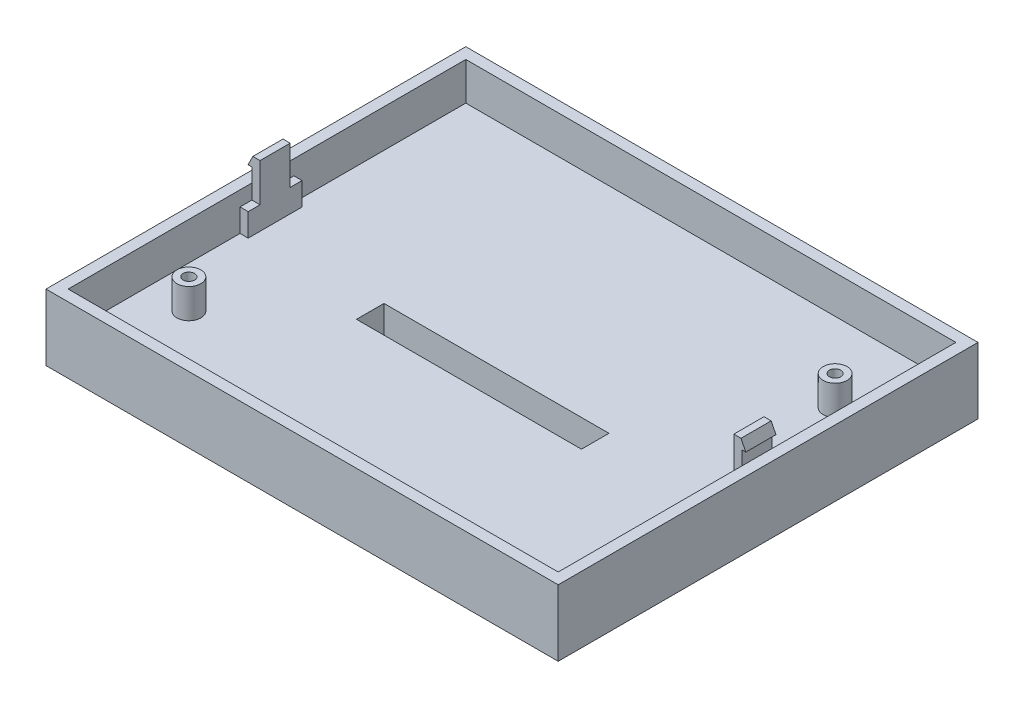
SolidWorks part; units mm, degrees
ref_plane "Alzado" through (0, 0, 0) normal (0, 0, 1) x (1, 0, 0)
ref_plane "Planta" through (0, 0, 0) normal (0, 1, 0) x (1, 0, 0)
ref_plane "Vista lateral" through (0, 0, 0) normal (1, 0, 0) x (0, 0, -1)
sketch "Sketch1" plane through (0, 0, 0) normal (0, 1, 0) x (1, 0, 0)
  line L1 (-53.5, -43.85) -> (53.5, -43.85)
  line L2 (-53.5, -43.85) -> (-53.5, 43.85)
  line L3 (-53.5, 43.85) -> (53.5, 43.85)
  line L4 (53.5, -43.85) -> (53.5, 43.85)
  line L5 (-53.5, -43.85) -> (53.5, 43.85) construction
  line L6 (-53.5, 43.85) -> (53.5, -43.85) construction
  point P0 (0, 0)
  dimension "D1" = 107
  dimension "D2" = 87.7
extrude "Boss-Extrude1" add sketch "Sketch1" along normal blind 13.85
sketch "Sketch2" plane through (0, 13.85, 0) normal (0, 1, 0) x (1, 0, 0)
  line L8 (51.19, -41.54) -> (51.19, 41.54)
  line L9 (51.19, 41.54) -> (-51.19, 41.54)
  line L10 (-51.19, 41.54) -> (-51.19, -41.54)
  line L11 (-51.19, -41.54) -> (51.19, -41.54)
  line L12 (51.19, -41.54) -> (51.19, 41.54)
  line L13 (51.19, 41.54) -> (-51.19, 41.54)
  line L14 (-51.19, 41.54) -> (-51.19, -41.54)
  line L15 (-51.19, -41.54) -> (51.19, -41.54)
  dimension "D1" = 2.31
extrude "Cut-Extrude1" cut sketch "Sketch2" against normal blind 7.9
sketch "Sketch3" plane through (0, 0, 0) normal (0, -1, 0) x (1, 0, 0)
  line L1 (-23.5, 14.74) -> (23.5, 14.74)
  line L7 (-23.5, 14.74) -> (-23.5, 3.2453)
  line L12 (53.5, 43.85) -> (53.5, -43.85) construction
  line L13 (53.5, -20.56) -> (53.5, 17.44)
  line L14 (0, 0) -> (0, 18.4212) construction
  line L23 (-6.19, -43.85) -> (6.19, -43.85)
  line L26 (53.5, -43.85) -> (-53.5, -43.85) construction
  line L27 (-23.5, 3.2453) -> (23.5, 3.2453)
  line L45 (23.5, 3.2453) -> (23.5, 14.74)
sketch "Sketch4" plane through (0, 5.95, 0) normal (0, 1, 0) x (1, 0, 0)
  circle A0 centre (42.5, 25) radius 1.2
  circle A1 centre (-42.5, -25) radius 1.2
  circle A2 centre (-42.5, -25) radius 2.5
  circle A3 centre (42.5, 25) radius 2.5
  dimension "D1" = 2.4
  dimension "D6" = 5
  dimension "D2" = 25
  dimension "D3" = 25
  dimension "D4" = 42.5
  dimension "D5" = 42.5
extrude "Boss-Extrude2" add sketch "Sketch4" along normal blind 6.2
sketch "Sketch7" plane through (-51.19, 0, 0) normal (1, 0, 0) x (0, 0, -1)
  line L0 (41.54, 5.95) -> (-41.54, 5.95) construction
  line L1 (-5.625, 5.95) -> (5.625, 5.95)
  line L2 (-5.625, 5.95) -> (-5.625, 10.75)
  line L3 (-5.625, 10.75) -> (5.625, 10.75)
  line L4 (5.625, 5.95) -> (5.625, 10.75)
  point P6 (0, 5.95)
  dimension "D1" = 11.25
  dimension "D2" = 4.8
extrude "Boss-Extrude3" add sketch "Sketch7" along normal blind 1.7
sketch "Sketch8" plane through (0, 0, 0) normal (0, 0, 1) x (1, 0, 0)
  line L0 (-49.49, 10.75) -> (-49.49, 18.75)
  line L1 (-49.49, 18.75) -> (-50.99, 18.75)
  line L2 (-50.99, 18.75) -> (-51.99, 16.75)
  line L3 (-51.99, 16.75) -> (-51.19, 16.75)
  line L4 (-51.19, 16.75) -> (-51.19, 10.75)
  line L5 (-51.19, 10.75) -> (-49.49, 10.75)
  line L6 (51.19, 5.95) -> (-51.19, 5.95) construction
  dimension "D1" = 12.8
  dimension "D2" = 2.5
  dimension "D3" = 2
  dimension "D4" = 1.5
extrude "Boss-Extrude4" add sketch "Sketch8" along normal mid plane 6.3
extrude "Boss-Extrude5" add sketch "Sketch3" along normal blind 4 contours L27 L14 L1 L7 | L14 L27 L45 L1 region at (-11.75, 0, 8.9926) region at (11.75, 0, 8.9926)
sketch "Sketch9" plane through (-23.5, 0, 0) normal (-1, 0, 0) x (0, 0, 1)
  line L0 (3.2453, 0) -> (3.2453, -2)
  line L4 (3.2453, -4) -> (3.2453, 0) construction
  line L5 (3.2453, -2) -> (10.6339, -2)
  line L6 (10.6339, -2) -> (10.6339, 0)
  line L7 (-43.85, 0) -> (43.85, 0) construction
  line L8 (10.6339, 0) -> (3.2453, 0)
extrude "Cut-Extrude2" cut sketch "Sketch9" against normal through all
sketch "Sketch10" plane through (0, 0, 0) normal (0, -1, 0) x (1, 0, 0)
  line L0 (-23.5, 3.2453) -> (23.5, 3.2453)
  line L1 (23.5, 3.2453) -> (23.5, 8.9926)
  line L2 (23.5, 3.2453) -> (23.5, 14.74) construction
  line L3 (23.5, 8.9926) -> (-23.5, 8.9926)
  line L4 (-23.5, 14.74) -> (-23.5, 3.2453) construction
  line L5 (-23.5, 8.9926) -> (-23.5, 3.2453)
extrude "Cut-Extrude4" cut sketch "Sketch10" against normal through all
chamfer "Chamfer1" distance 2 angle 45 1 edges at (0, -2, 3.2453)
mirror "Mirror1" about plane through (0, 0, 0) normal (1, 0, 0) of "Boss-Extrude3", "Boss-Extrude4"
sketch "Sketch14" plane through (0, 0, 0) normal (0, -1, 0) x (1, 0, 0)
  line L0 (-23.5, 14.74) -> (-35.1845, 14.74)
  line L1 (-35.1845, 14.74) -> (-35.1845, 0)
  line L2 (-35.1845, 0) -> (-46.8935, 0)
  line L3 (-46.8935, 0) -> (-46.8935, -23.4181)
  line L4 (-23.5, 10.6339) -> (-29.7078, 10.6339)
  line L5 (-29.7078, 10.6339) -> (-29.7078, -4.0716)
  line L6 (-29.7078, -4.0716) -> (-41.6181, -4.0716)
  line L7 (-41.6181, -4.0716) -> (-41.6181, -23.4181)
  line L8 (-41.6181, -23.4181) -> (-46.8935, -23.4181)
  line L9 (-23.5, 14.74) -> (-23.5, 10.6339)
  line L13 (23.5, 10.6339) -> (23.5, 14.74)
  line L14 (-23.5, 10.6339) -> (23.5, 10.6339)
  line L15 (-23.5, 14.74) -> (-23.5, 10.6339)
  line L16 (23.5, 14.74) -> (-23.5, 14.74)
  line L17 (23.5, 10.6339) -> (23.5, 14.74)
  line M20 (-23.5, 10.6339) -> (-23.5, 14.74)
  dimension "D1" = 0
extrude "Boss-Extrude7" add sketch "Sketch14" along normal blind 1.5 contours L8 L7 L6 L5 L4 L0 L1 L2 L3 M20 region at (-37.7149, 0, -2.2531)
mirror "Mirror2" about plane through (0, 0, 0) normal (1, 0, 0) of "Boss-Extrude7"
